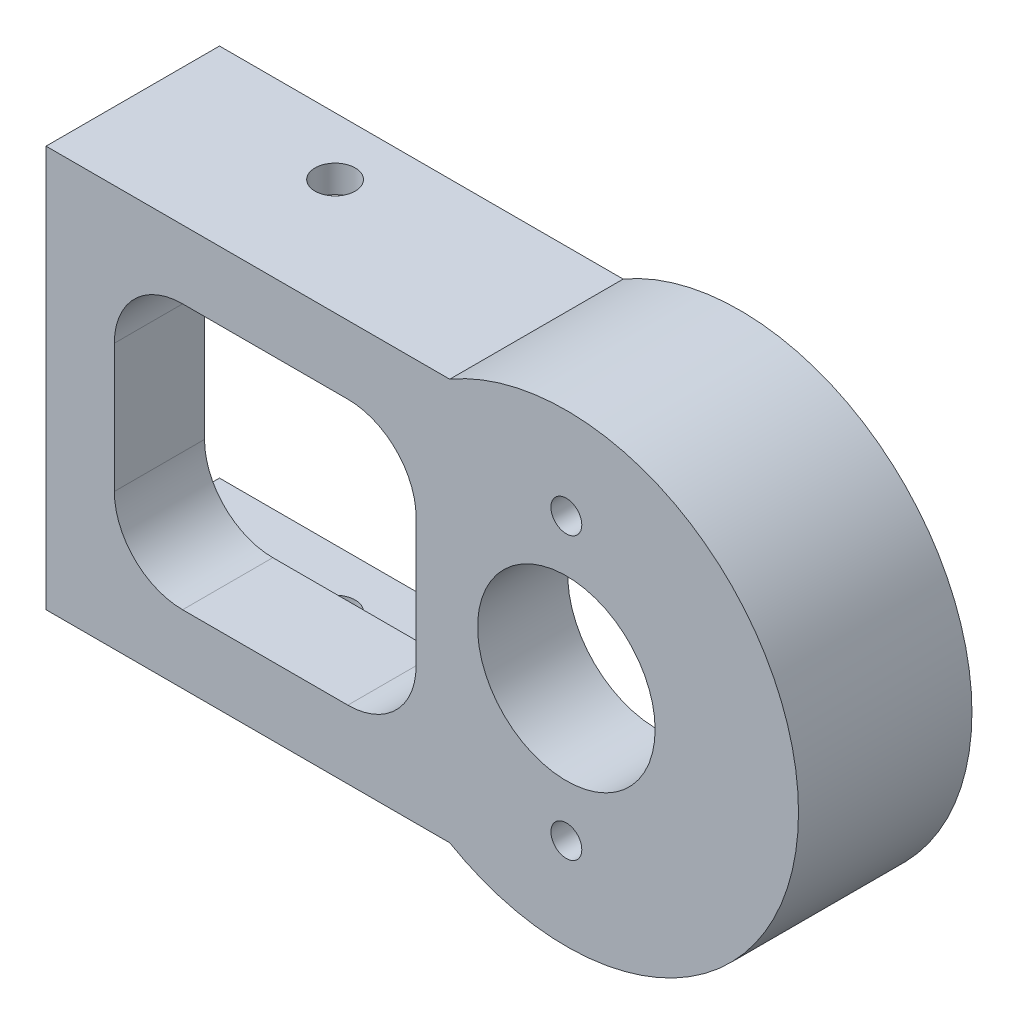
SolidWorks part; units mm, degrees
ref_plane "Front Plane" through (0, 0, 0) normal (0, 0, 1) x (1, 0, 0)
ref_plane "Top Plane" through (0, 0, 0) normal (0, 1, 0) x (1, 0, 0)
ref_plane "Right Plane" through (0, 0, 0) normal (1, 0, 0) x (0, 0, -1)
sketch "Sketch2" plane through (0, 0, 0) normal (0, 0, 1) x (1, 0, 0)
  line L0 (-38.1, -14.7) -> (0, -14.7) construction
  line L1 (-38.1, -14.7) -> (-38.1, 14.7)
  line L3 (-38.1, 14.7) -> (0, 14.7) construction
  line L4 (-38.1, -14.7) -> (0, 14.7) construction
  line L5 (0, -14.7) -> (-38.1, 14.7) construction
  line L6 (0, 0) -> (-63.6035, 0) construction
  line L7 (-38.1, 14.7) -> (-8.5387, 14.7)
  line L8 (-8.5387, -14.7) -> (-38.1, -14.7)
  line L9 (0, 10.2947) -> (0, -10.2947) construction
  line L10 (0, 14.7) -> (0, -14.7) construction
  line L12 (-11, 9.7) -> (-33.1, 9.7)
  line L13 (-11, 9.7) -> (-11, -9.7)
  line L14 (-11, -9.7) -> (-33.1, -9.7)
  line L15 (-33.1, 9.7) -> (-33.1, -9.7)
  line L16 (-11, 9.7) -> (-33.1, -9.7) construction
  line L17 (-11, -9.7) -> (-33.1, 9.7) construction
  circle A0 centre (0, 0) radius 17 construction
  arc A1 (-8.5387, -14.7) -> (-8.5387, 14.7) centre (0, 0) ccw
  circle A2 centre (0, 0) radius 6.5
  circle A3 centre (0, -10.2947) radius 1.1303
  circle A4 centre (0, 10.2947) radius 1.1303
  point P3 (-38.1, 0)
  point P4 (-19.05, 0)
  point P11 (-22.05, 0)
  point P20 (0, 0)
  point P24 (-11, 0)
  dimension "D1" = 34
  dimension "D4" = 13
  dimension "D5" = 2.2606
  dimension "D2" = 29.4
  dimension "D3" = 38.1
  dimension "D6" = 5
  dimension "D7" = 11
  dimension "D8" = 5
extrude "Boss-Extrude1" add sketch "Sketch2" along normal blind 12.7
sketch "Sketch1" plane through (0, 0, 0) normal (0, 0, 1) x (1, 0, 0)
  line L0 (-38.1, -12.7) -> (0, -12.7) construction
  line L1 (-38.1, -12.7) -> (-38.1, 12.7)
  line L2 (0, -12.7) -> (0, 12.7) construction
  line L3 (-38.1, 12.7) -> (0, 12.7) construction
  line L4 (-38.1, -12.7) -> (0, 12.7) construction
  line L5 (0, -12.7) -> (-38.1, 12.7) construction
  line L6 (-20.0762, 0) -> (0, 0) construction
  line L7 (-38.1, 14.7) -> (-38.1, -14.7) construction
  line L8 (-7.9819, 12.7) -> (-38.1, 12.7)
  line L9 (-7.9819, -12.7) -> (-38.1, -12.7)
  circle A1 centre (0, 0) radius 15 construction
  arc A2 (-7.9819, -12.7) -> (-7.9819, 12.7) centre (0, 0) ccw
  point P5 (-19.05, 0)
  point P7 (-38.1, 0)
  point P12 (0, 0)
  dimension "D1" = 30
  dimension "D2" = 25.4
extrude "Cut-Extrude1" cut sketch "Sketch1" along normal blind 6.096
fillet "Fillet1" radius 5 4 edges at (-33.1, 9.7, 9.398) (-11, 9.7, 9.398) (-33.1, -9.7, 9.398) (-11, -9.7, 9.398)
sketch "Sketch3" plane through (0, -14.7, 0) normal (0, -1, 0) x (1, 0, 0)
  line L0 (-35.5488, 6.096) -> (-18.3126, 6.096) construction
  line L1 (-38.1, 6.096) -> (-7.9819, 6.096) construction
  line L2 (0, 0) -> (0, 18) construction
  circle A0 centre (-25.4, 4.2345) radius 1.4732
  dimension "D2" = 2.9464
  dimension "D1" = 25.4
extrude "Cut-Extrude2" cut sketch "Sketch3" against normal through all both and the other way through all contours A0
